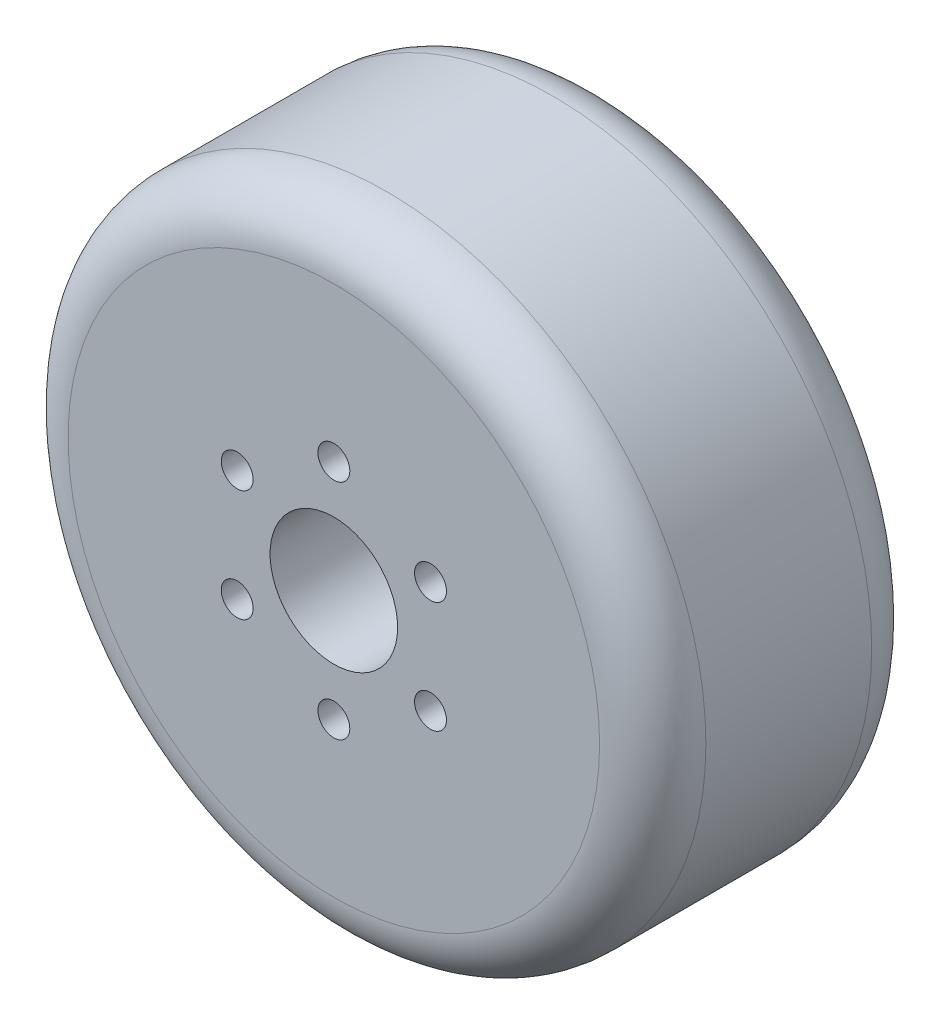
SolidWorks part; units mm, degrees
ref_plane "正面" through (0, 0, 0) normal (0, 0, 1) x (1, 0, 0)
ref_plane "平面" through (0, 0, 0) normal (0, 1, 0) x (1, 0, 0)
ref_plane "右側面" through (0, 0, 0) normal (1, 0, 0) x (0, 0, -1)
sketch "ｽｹｯﾁ1" plane through (0, 0, 0) normal (0, 0, 1) x (1, 0, 0)
  line L0 (0, 0) -> (0, 10.5) construction
  circle A0 centre (0, 0) radius 30
  circle A1 centre (0, 0) radius 6
  circle A2 centre (0, 10.5) radius 1.5 construction
  circle A3 centre (0, 0) radius 10.5 construction
  dimension "D1" = 60
  dimension "D2" = 12
  dimension "D3" = 21
  dimension "D4" = 3
extrude "ﾎﾞｽ - 押し出し1" add sketch "ｽｹｯﾁ1" along normal blind 25.6
fillet "ﾌｨﾚｯﾄ2" radius 5 2 edges at (30, 0, 25.6) (30, 0, 0)
sketch "ｽｹｯﾁ3" plane through (0, 0, 0) normal (0, 0, -1) x (-1, 0, 0)
  circle A0 centre (0, 0) radius 10.5 construction
  circle A1 centre (0, 10.5) radius 1.5
  dimension "D1" = 21
  dimension "D2" = 3
extrude "ｶｯﾄ - 押し出し1" cut sketch "ｽｹｯﾁ3" against normal through all
pattern_circular "円形ﾊﾟﾀｰﾝ2" count 6 over 360 about axis through (0, 0, 25.6) along (0, 0, -1) of "ｶｯﾄ - 押し出し1"
